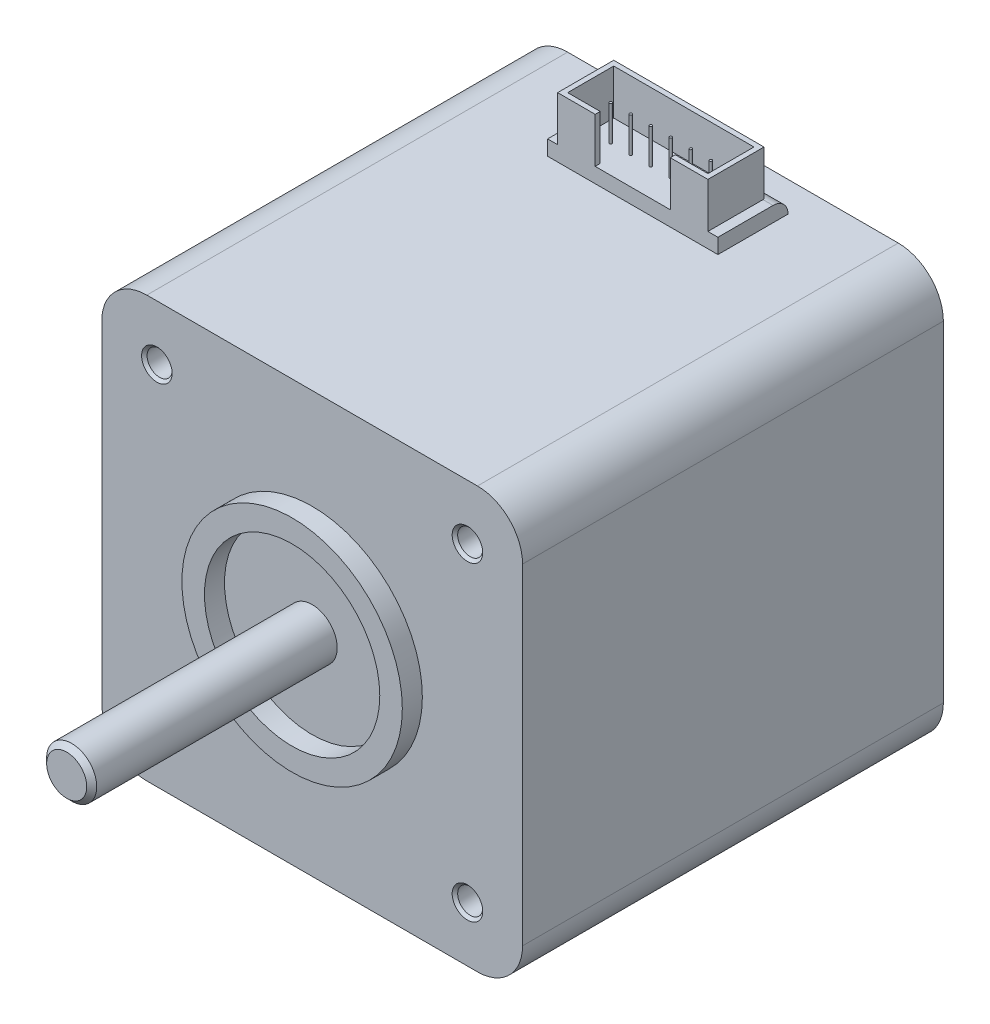
SolidWorks part; units mm, degrees
material "1060 Alloy"
ref_plane "Front Plane" through (0, 0, 0) normal (0, 0, 1) x (1, 0, 0)
ref_plane "Top Plane" through (0, 0, 0) normal (0, 1, 0) x (1, 0, 0)
ref_plane "Right Plane" through (0, 0, 0) normal (1, 0, 0) x (0, 0, -1)
sketch "Sketch1" plane through (0, 0, 0) normal (0, 0, 1) x (1, 0, 0)
  line L1 (-29.6154, 19.2115) -> (12.3846, 19.2115)
  line L2 (-29.6154, 19.2115) -> (-29.6154, -22.7885)
  line L3 (-29.6154, -22.7885) -> (12.3846, -22.7885)
  line L4 (12.3846, 19.2115) -> (12.3846, -22.7885)
  dimension "D1" = 42
  dimension "D2" = 42
extrude "Boss-Extrude2" add sketch "Sketch1" along normal blind 8
sketch "Sketch2" plane through (0, 0, 8) normal (0, 0, 1) x (1, 0, 0)
  line L0 (12.3846, -22.7885) -> (12.3846, 19.2115) construction
  line L1 (-29.6154, -1.7885) -> (12.3846, -1.7885) construction
  line L2 (-29.6154, 19.2115) -> (-29.6154, -22.7885) construction
  circle A0 centre (-8.6154, -1.7885) radius 11
  point P3 (0, 0)
  point P9 (-8.6154, -1.7885)
  dimension "D1" = 22
extrude "Boss-Extrude3" add sketch "Sketch2" along normal blind 2
sketch "Sketch4" plane through (0, 0, 0) normal (0, 0, -1) x (-1, 0, 0)
  line L1 (-12.3846, 19.2115) -> (29.6154, 19.2115)
  line L2 (-12.3846, 19.2115) -> (-12.3846, -22.7885)
  line L3 (-12.3846, -22.7885) -> (29.6154, -22.7885)
  line L4 (29.6154, 19.2115) -> (29.6154, -22.7885)
extrude "Boss-Extrude5" add sketch "Sketch4" along normal blind 24
sketch "Sketch5" plane through (0, 0, -24) normal (0, 0, -1) x (-1, 0, 0)
  line L1 (-12.3846, 19.2115) -> (29.6154, 19.2115)
  line L2 (-12.3846, 19.2115) -> (-12.3846, -22.7885)
  line L3 (-12.3846, -22.7885) -> (29.6154, -22.7885)
  line L4 (29.6154, 19.2115) -> (29.6154, -22.7885)
extrude "Boss-Extrude6" add sketch "Sketch5" along normal blind 10
fillet "Fillet1" radius 4.5 4 edges at (12.3846, 19.2115, -13) (-29.6154, -22.7885, -13) (12.3846, -22.7885, -13) (-29.6154, 19.2115, -13)
sketch "Sketch7" plane through (0, 0, -34) normal (0, 0, -1) x (-1, 0, 0)
  line L0 (-12.3846, -1.7885) -> (29.6154, -1.7885) construction
  line L1 (-12.3846, 14.7115) -> (-12.3846, -18.2885) construction
  line L2 (29.6154, -18.2885) -> (29.6154, 14.7115) construction
  circle A0 centre (8.6154, -1.7885) radius 8.75
  point P8 (0, 0)
  point P9 (0, 0)
  point P10 (8.6154, -1.7885)
  dimension "D1" = 17.5
extrude "Cut-Extrude1" cut sketch "Sketch7" against normal blind 2
sketch "Sketch8" plane through (0, 0, 10) normal (0, 0, 1) x (1, 0, 0)
  circle A0 centre (-8.6154, -1.7885) radius 8.75
  dimension "D1" = 17.5
extrude "Cut-Extrude2" cut sketch "Sketch8" against normal blind 2
sketch "Sketch9" plane through (0, 0, 8) normal (0, 0, 1) x (1, 0, 0)
  circle A0 centre (-8.6154, -1.7885) radius 2.5
  dimension "D1" = 5
extrude "Boss-Extrude9" add sketch "Sketch9" along normal blind 24.5
chamfer "Chamfer2" distance 0.5 angle 45 1 edges at (-6.1154, -1.7885, 32.5)
sketch "Sketch10" plane through (0, 0, 8) normal (0, 0, 1) x (1, 0, 0)
  line L0 (12.3846, -18.2885) -> (12.3846, 14.7115) construction
  line L1 (-24.1154, 13.7115) -> (6.8846, 13.7115) construction
  line L2 (-24.1154, 13.7115) -> (-24.1154, -17.2885) construction
  line L3 (-24.1154, -17.2885) -> (6.8846, -17.2885) construction
  line L4 (6.8846, 13.7115) -> (6.8846, -17.2885) construction
  line L5 (-25.1154, -22.7885) -> (7.8846, -22.7885) construction
  circle A0 centre (-24.1154, 13.7115) radius 1.6 construction
  circle A1 centre (-24.1154, -17.2885) radius 1.6 construction
  circle A2 centre (6.8846, -17.2885) radius 1.6 construction
  circle A3 centre (6.8846, 13.7115) radius 1.6 construction
  dimension "D1" = 3.2
  dimension "D2" = 31
  dimension "D3" = 31
  dimension "D4" = 5.5
  dimension "D5" = 5.5
hole_wizard "M3x0.5 Tapped Hole1" positions "3DSketch1" profile "Sketch11" tap size "M3x0.5" standard "ANSI Metric"
sketch3d "3DSketch1"
  point P0 (-24.1154, 13.7115, 8)
  point P3 (6.8846, 13.7115, 8)
  point P6 (6.8846, -17.2885, 8)
  point P9 (-24.1154, -17.2885, 8)
sketch "Sketch11" plane through (-24.1154, 13.7115, 8) normal (1, 0, 0) x (0, -1, 0)
  line L0 (0, 0) -> (0, 6.5011)
  line L1 (0, 6.5011) -> (1.25, 5.75)
  line L2 (1.25, 5.75) -> (1.25, 0.275)
  line L3 (1.25, 0.275) -> (1.525, 0)
  line L5 (1.525, 0) -> (0, 0)
  line L6 (-1.25, 0.275) -> (-1.525, 0) construction
  line L10 (0, 6.5011) -> (-1.25, 5.75) construction
  line L11 (0, -6.35) -> (0, 107.95) construction
  dimension "Tap Drill Dia." = 2.5
  dimension "Tap Drill Depth" = 5.75
  dimension "Near C'Sink Dia." = 3.05
  dimension "Near C'Sink Angle" = 90
  dimension "Drill Angle" = 118
cosmetic thread "Hole Thread1" parameters "D1"=4, "D2"=3
cosmetic thread "Hole Thread2" parameters "D1"=4, "D2"=3
cosmetic thread "Hole Thread3" parameters "D1"=4, "D2"=3
cosmetic thread "Hole Thread4" parameters "D1"=4, "D2"=3
sketch "Sketch12" plane through (0, 19.2115, 0) normal (0, 1, 0) x (1, 0, 0)
  line L0 (12.3846, 34) -> (-29.6154, 34) construction
  line L1 (-17.1154, 31) -> (-0.1154, 31)
  line L2 (-17.1154, 31) -> (-17.1154, 24)
  line L3 (-17.1154, 24) -> (-0.1154, 24)
  line L4 (-0.1154, 31) -> (-0.1154, 24)
  line L5 (12.3846, -8) -> (12.3846, 34) construction
  point P6 (-8.6154, 31)
  dimension "D1" = 17
  dimension "D2" = 7
  dimension "D3" = 10
  dimension "D4" = 21
extrude "Boss-Extrude10" add sketch "Sketch12" along normal blind 1.5
fillet "Fillet2" radius 1.5 1 edges at (-8.6154, 20.7115, -31)
sketch "Sketch13" plane through (0, 20.7115, 0) normal (0, 1, 0) x (1, 0, 0)
  line L0 (-17.1154, 24) -> (-0.1154, 24) construction
  line L1 (-16.1154, 29.6) -> (-1.1154, 29.6)
  line L2 (-16.1154, 29.6) -> (-16.1154, 24)
  line L3 (-16.1154, 24) -> (-1.1154, 24)
  line L4 (-1.1154, 29.6) -> (-1.1154, 24)
  line L7 (-17.1154, 31) -> (-17.1154, 24) construction
  point P12 (-8.6154, 24)
  dimension "D1" = 15
  dimension "D2" = 5.6
  dimension "D3" = 8.5
extrude "Boss-Extrude11" add sketch "Sketch13" along normal blind 4.5
sketch "Sketch15" plane through (0, 25.2115, 0) normal (0, 1, 0) x (1, 0, 0)
  line L0 (-12.3654, 24) -> (-12.3654, 24.5)
  line L1 (-16.1154, 24) -> (-1.1154, 24) construction
  line L2 (-12.3654, 24.5) -> (-15.6154, 24.5)
  line L3 (-15.6154, 24.5) -> (-15.6154, 29.1)
  line L4 (-15.6154, 29.1) -> (-1.6154, 29.1)
  line L5 (-1.6154, 29.1) -> (-1.6154, 24.5)
  line L6 (-1.6154, 24.5) -> (-4.8654, 24.5)
  line L7 (-4.8654, 24.5) -> (-4.8654, 24)
  line L8 (-17.1154, 24) -> (-0.1154, 24) construction
  line L9 (-12.3654, 24) -> (-4.8654, 24)
  line L10 (-1.1154, 24) -> (-1.1154, 29.5) construction
  line L11 (-1.1154, 29.6) -> (-16.1154, 29.6) construction
  dimension "D1" = 7.5
  dimension "D2" = 14
  dimension "D3" = 0.5
  dimension "D4" = 0.5
  dimension "D5" = 3.25
  dimension "D6" = 0.5
extrude "Cut-Extrude3" cut sketch "Sketch15" against normal blind 4.5
sketch "Sketch16" plane through (0, 20.7115, 0) normal (0, 1, 0) x (1, 0, 0)
  line L0 (-1.6154, 29.1) -> (-15.6154, 29.1) construction
  line L1 (-15.6154, 29.1) -> (-15.6154, 24.5) construction
  circle A0 centre (-13.6154, 26.8) radius 0.125
  point P6 (0, 0)
  point P7 (0, 0)
  point P8 (0, 0)
  dimension "D1" = 0.25
  dimension "D2" = 2.3
  dimension "D3" = 2
extrude "Boss-Extrude12" add sketch "Sketch16" along normal blind 3.5 contours A0
pattern_linear "LPattern1" count 6 spacing 2 along (1, 0, 0) of "Boss-Extrude12"
